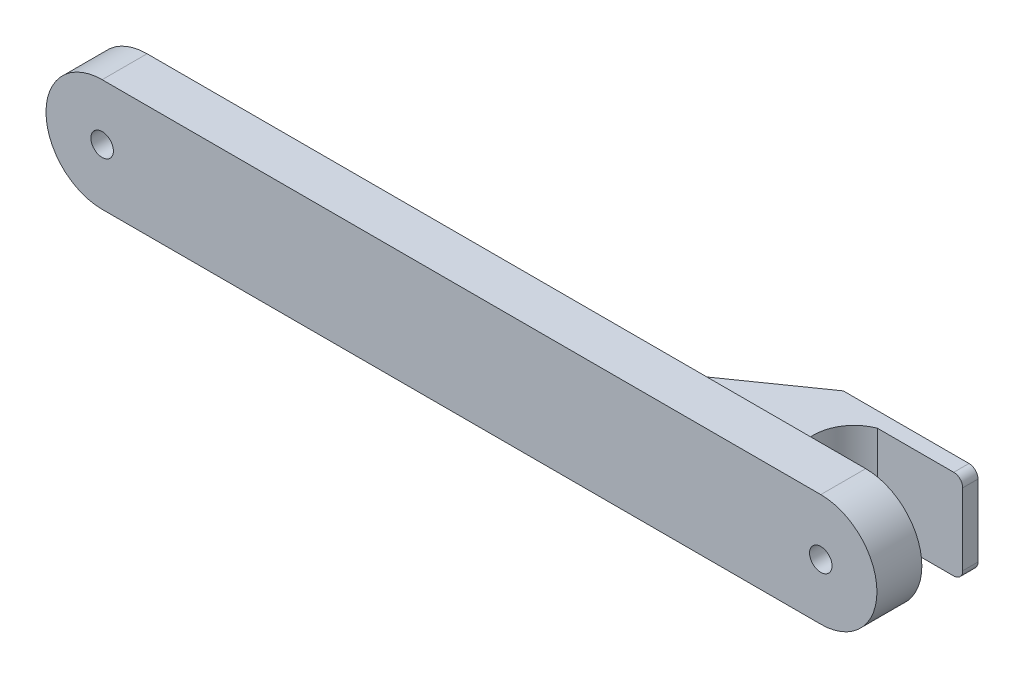
SolidWorks part; units mm, degrees
ref_plane "Front" through (0, 0, 0) normal (0, 0, 1) x (1, 0, 0)
ref_plane "Top" through (0, 0, 0) normal (0, 1, 0) x (1, 0, 0)
ref_plane "Right" through (0, 0, 0) normal (1, 0, 0) x (0, 0, -1)
sketch "Sketch1" plane through (0, 0, 0) normal (0, 0, 1) x (1, 0, 0)
  line L0 (299.8703, -79.0606) -> (503.0703, -79.0606) construction
  line L1 (299.8703, -63.1856) -> (503.0703, -63.1856)
  line L2 (299.8703, -94.9356) -> (503.0703, -94.9356)
  line L3 (401.4703, -94.9356) -> (401.4703, -63.1856) construction
  arc A0 (299.8703, -63.1856) -> (299.8703, -94.9356) centre (299.8703, -79.0606) ccw
  arc A1 (503.0703, -94.9356) -> (503.0703, -63.1856) centre (503.0703, -79.0606) ccw
  circle A2 centre (299.8703, -79.0606) radius 3.175
  circle A3 centre (503.0703, -79.0606) radius 3.175
  point P2 (401.4703, -79.0606)
  dimension "D1" = 203.2
  dimension "D2" = 15.875
  dimension "D3" = 31.75
extrude "Boss-Extrude1" add sketch "Sketch1" along normal blind 12.7
sketch "Sketch2" plane through (0, 0, 0) normal (0, 0, -1) x (-1, 0, 0)
  line L5 (-477.6703, -66.3606) -> (-477.6703, -91.7606)
  line L6 (-513.2303, -91.7606) -> (-477.6703, -91.7606)
  line L7 (-515.7703, -89.2206) -> (-515.7703, -68.9006)
  line L8 (-513.2303, -66.3606) -> (-477.6703, -66.3606)
  line L10 (-515.7703, -91.7606) -> (-490.3703, -66.3606) construction
  line L11 (-515.7703, -66.3606) -> (-490.3703, -91.7606) construction
  arc A0 (-513.2303, -91.7606) -> (-515.7703, -89.2206) centre (-513.2303, -89.2206) cw
  arc A3 (-515.7703, -68.9006) -> (-513.2303, -66.3606) centre (-513.2303, -68.9006) cw
  point P0 (-503.0703, -79.0606)
  dimension "D3" = 2.54
  dimension "D1" = 25.4
  dimension "D2" = 25.4
  dimension "D4" = 35.56
extrude "Boss-Extrude2" add sketch "Sketch2" along normal blind 19.05
sketch "Sketch4" plane through (0, -91.7606, 0) normal (0, -1, 0) x (1, 0, 0)
  line L0 (477.6703, -19.05) -> (450.464, 0)
  line L1 (299.8703, 0) -> (503.0703, 0) construction
  line L2 (450.464, 0) -> (477.6703, 0)
  line L3 (477.6703, 0) -> (477.6703, -19.05)
  dimension "D2" = 19.05
  dimension "D4" = 27.2062
  dimension "D1" = 215
  dimension "D3" = 33.2127
sketch "Sketch6" plane through (0, -91.7606, 0) normal (0, -1, 0) x (1, 0, 0)
  line L1 (515.7703, -19.05) -> (515.7703, 0) construction
  line L2 (499.2461, 0) -> (515.7703, 0)
  line L3 (512.5953, 0) -> (477.6703, 0) construction
  line L6 (491.6403, -14.7335) -> (515.7703, -14.7335)
  line L7 (515.7703, -14.7335) -> (515.7703, 0)
  line L10 (299.8703, 0) -> (503.0703, 0) construction
  line L11 (512.5953, 0) -> (477.6703, 0) construction
  line L12 (485.0369, 0) -> (488.9084, 0)
  line L13 (488.9084, 0) -> (499.2461, 0)
  arc A2 (491.6403, -14.7335) -> (485.0369, 0) centre (495.7053, -4.0651) cw
  point P10 (485.0369, 0)
  dimension "D2" = 11.4166
  dimension "D1" = 24.13
  dimension "D3" = 30.7333
  dimension "D4" = 14.7335
extrude "Cut-Extrude2" cut sketch "Sketch6" against normal blind 30.48
extrude "Boss-Extrude7" add sketch "Sketch4" against normal blind 25.4
ref_plane "Plane5" through (401.447, 0, 0) normal (1, 0, 0) x (0, 0, -1)
ref_plane "Plane6" through (401.4703, 0, 0) normal (1, 0, 0) x (0, 0, -1)
ref_plane "Plane7" through (0, 0, 6.3485) normal (0, 0, 1) x (1, 0, 0)
surface "Surface-MidSurface2" parameters "D0"=50000
sketch "Sketch7" plane through (0, 0, 12.7) normal (0, 0, 1) x (1, 0, 0)
  line L0 (310.0303, -66.3606) -> (312.5703, -66.3606)
  line L1 (289.7103, -91.7606) -> (310.0303, -91.7606)
  line L2 (287.1703, -89.2206) -> (287.1703, -68.9006)
  line L3 (289.7103, -66.3606) -> (310.0303, -66.3606)
  line L5 (287.1703, -91.7606) -> (312.5703, -66.3606) construction
  line L6 (287.1703, -66.3606) -> (312.5703, -91.7606) construction
  line L7 (312.5703, -66.3606) -> (322.7303, -66.3606)
  line L8 (322.7303, -66.3606) -> (322.7303, -91.7606)
  line L9 (310.0303, -91.7606) -> (322.7303, -91.7606)
  arc A0 (289.7103, -91.7606) -> (287.1703, -89.2206) centre (289.7103, -89.2206) cw
  arc A3 (287.1703, -68.9006) -> (289.7103, -66.3606) centre (289.7103, -68.9006) cw
  point P0 (299.8703, -79.0606)
  dimension "D3" = 2.54
  dimension "D1" = 25.4
  dimension "D2" = 25.4
  dimension "D4" = 10.16
